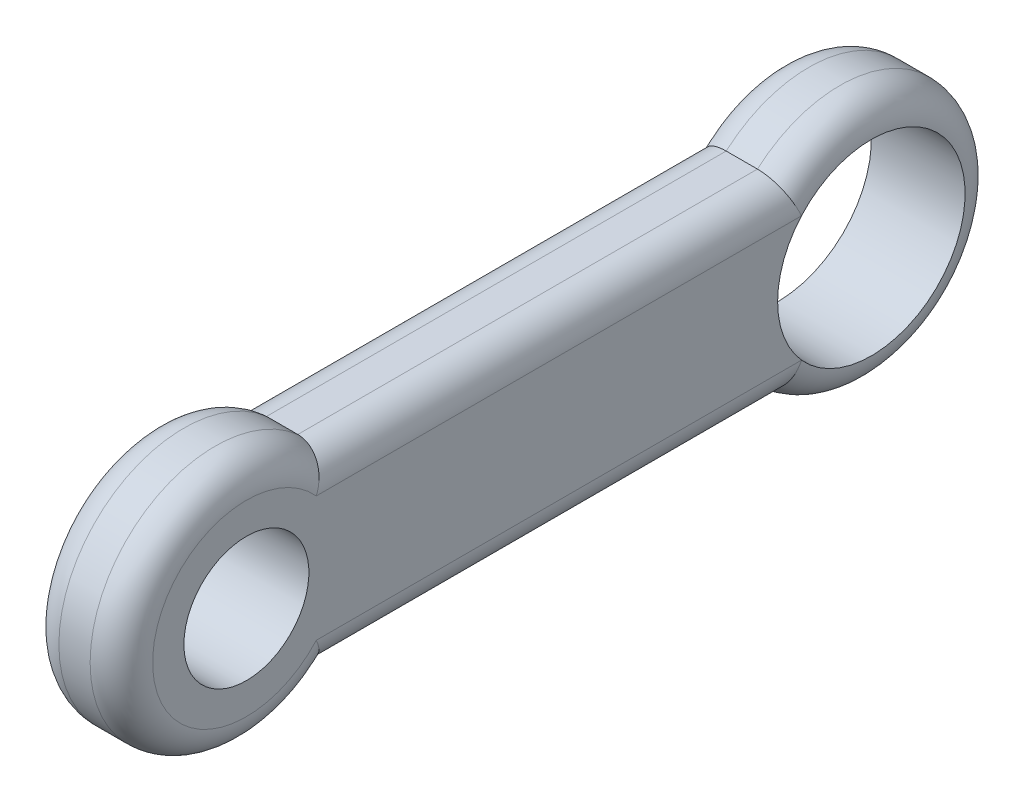
SolidWorks part; units mm, degrees
ref_plane "Front Plane" through (0, 0, 0) normal (0, 0, 1) x (1, 0, 0)
ref_plane "Top Plane" through (0, 0, 0) normal (0, 1, 0) x (1, 0, 0)
ref_plane "Right Plane" through (0, 0, 0) normal (1, 0, 0) x (0, 0, -1)
sketch "Sketch1" plane through (0, 0, 0) normal (1, 0, 0) x (0, 0, -1)
  line L0 (0, 0) -> (-20, 0) construction
  line L1 (55, 0) -> (-55, 0) construction
  line L2 (0, 0) -> (-20, 0) construction
  line L3 (-2.6458, -3) -> (-17.3542, -3)
  line L4 (-2.6458, 3) -> (-17.3542, 3)
  arc A2 (-17.3542, 3) -> (-17.3542, -3) centre (-20, 0) ccw
  arc A3 (-2.6458, -3) -> (-2.6458, 3) centre (0, 0) ccw
  point P5 (-10, 0)
extrude "Boss-Extrude1" add sketch "Sketch1" along normal blind 3
sketch "Sketch2" plane through (0, 0, 0) normal (1, 0, 0) x (0, 0, -1)
  circle A1 centre (0, 0) radius 3
  dimension "D1" = 6
extrude "Cut-Extrude1" cut sketch "Sketch2" along normal blind 3 contours A1
sketch "Sketch3" plane through (0, 0, 0) normal (-1, 0, 0) x (0, 0, 1)
  circle A0 centre (20, 0) radius 2
  dimension "D1" = 4
extrude "Cut-Extrude2" cut sketch "Sketch3" against normal blind 3
fillet "Fillet1" radius 1 8 edges at (3, 0, -4) (3, -3, 10) (3, 0, 24) (3, 3, 10) (0, 0, 24) (0, -3, 10) (0, 0, -4) (0, 3, 10)
scale "Scale1" scale about origin uniform scaling yes scale factor 1.5
